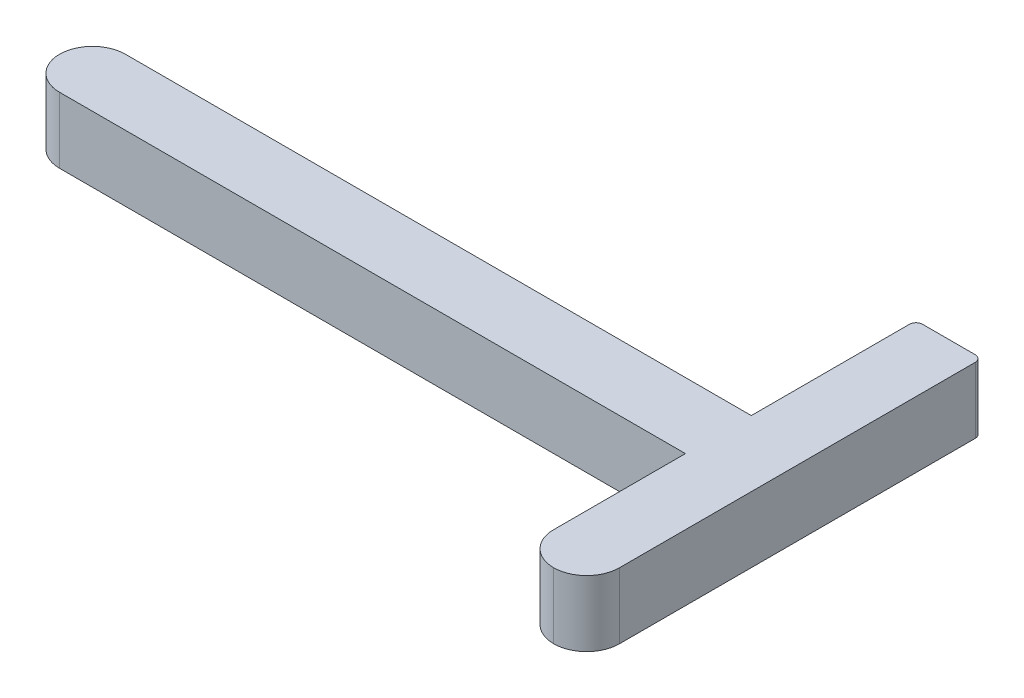
SolidWorks part; units mm, degrees
ref_plane "Plan de face" through (0, 0, 0) normal (0, 0, 1) x (1, 0, 0)
ref_plane "Plan de dessus" through (0, 0, 0) normal (0, 1, 0) x (1, 0, 0)
ref_plane "Plan de droite" through (0, 0, 0) normal (1, 0, 0) x (0, 0, -1)
sketch "Esquisse1" plane through (0, 0, 0) normal (0, 1, 0) x (1, 0, 0)
  line L0 (50, 30) -> (50, 5)
  line L1 (50, -5) -> (-50, -5)
  line L3 (50, 5) -> (-50, 5)
  line L4 (-50, -5) -> (-50, 5)
  line L5 (50, -5) -> (-50, 5) construction
  line L6 (50, 5) -> (-50, -5) construction
  line L7 (50, -30) -> (60, -30)
  line L9 (50, 30) -> (60, 30)
  line L10 (60, -30) -> (60, 30)
  line L11 (50, -5) -> (50, -30)
  point P0 (0, 0)
  dimension "D1" = 100
  dimension "D2" = 10
  dimension "D3" = 10
  dimension "D4" = 25
  dimension "D5" = 25
extrude "Boss.-Extru.1" add sketch "Esquisse1" along normal blind 10 contours L3 L4 L1 L11 L7 L10 L9 L0
fillet "Congé3" radius 5 2 edges at (60, 5, 30) (50, 5, 30)
fillet "Congé4" radius 5 2 edges at (-50, 5, 5) (-50, 5, -5)
fillet "Congé5" radius 1 1 edges at (50, 5, -30)
fillet "Congé6" radius 1 1 edges at (60, 5, -30)
sketch3d "Esquisse3D1"
  line L0 (-50, 10, 0) -> (-50, 0, 0) construction
  line L2 (-50, 4.5, -1.5) -> (-50, 4.5, 1.5)
  line L3 (-50, 4.5, -1.5) -> (-50, 5.5, -1.5)
  line L4 (-50, 5.5, -1.5) -> (-50, 5.5, 1.5)
  line L5 (-50, 4.5, 1.5) -> (-50, 5.5, 1.5)
  line L6 (-50, 4.5, -1.5) -> (-50, 5.5, 1.5) construction
  line L7 (-50, 5.5, -1.5) -> (-50, 4.5, 1.5) construction
  point P2 (-50, 5, 0)
  dimension "D1" = 3
  dimension "D2" = 1
extrude "Enlèv. mat.-Extru.1" cut sketch "Esquisse3D1" along direction (-1, 0, 0) on the side against the normal blind 30
